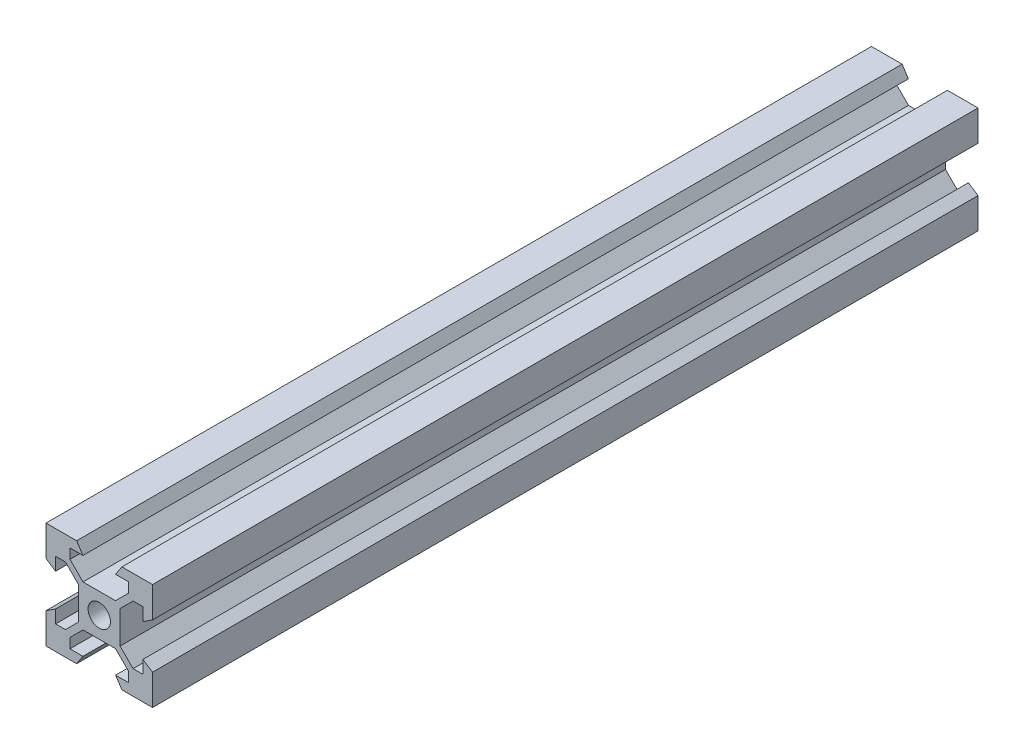
SolidWorks part; units mm, degrees
ref_plane "Front Plane" through (0, 0, 0) normal (0, 0, 1) x (1, 0, 0)
ref_plane "Top Plane" through (0, 0, 0) normal (0, 1, 0) x (1, 0, 0)
ref_plane "Right Plane" through (0, 0, 0) normal (1, 0, 0) x (0, 0, -1)
sketch "Sketch1" plane through (0, 0, 0) normal (0, 0, 1) x (1, 0, 0)
  line L0 (-10, 10) -> (-4.25, 10)
  line L1 (-4.25, 10) -> (-3.065, 8.2)
  line L2 (-3.065, 8.2) -> (-5.5, 8.2)
  line L3 (-5.5, 8.2) -> (-5.5, 6.3485)
  line L4 (-5.5, 6.3485) -> (-3.0515, 3.9)
  line L5 (-3.0515, 3.9) -> (0, 3.9)
  line L6 (-10, 10) -> (0, 0) construction
  line L7 (-3.9, 3.0515) -> (-3.9, 0)
  line L8 (-6.3485, 5.5) -> (-3.9, 3.0515)
  line L9 (-8.2, 3.065) -> (-8.2, 5.5)
  line L10 (-8.2, 5.5) -> (-6.3485, 5.5)
  line L11 (-10, 4.25) -> (-8.2, 3.065)
  line L12 (-10, 10) -> (-10, 4.25)
  line L13 (10, 10) -> (10, 4.25)
  line L14 (10, 10) -> (4.25, 10)
  line L15 (4.25, 10) -> (3.065, 8.2)
  line L16 (3.065, 8.2) -> (5.5, 8.2)
  line L17 (5.5, 8.2) -> (5.5, 6.3485)
  line L18 (8.2, 5.5) -> (6.3485, 5.5)
  line L19 (8.2, 3.065) -> (8.2, 5.5)
  line L20 (10, 4.25) -> (8.2, 3.065)
  line L21 (3.9, 3.0515) -> (3.9, 0)
  line L22 (6.3485, 5.5) -> (3.9, 3.0515)
  line L23 (5.5, 6.3485) -> (3.0515, 3.9)
  line L24 (3.0515, 3.9) -> (0, 3.9)
  line L25 (10, -10) -> (4.25, -10)
  line L26 (10, -10) -> (10, -4.25)
  line L27 (10, -4.25) -> (8.2, -3.065)
  line L28 (8.2, -3.065) -> (8.2, -5.5)
  line L29 (8.2, -5.5) -> (6.3485, -5.5)
  line L30 (5.5, -8.2) -> (5.5, -6.3485)
  line L31 (3.065, -8.2) -> (5.5, -8.2)
  line L32 (4.25, -10) -> (3.065, -8.2)
  line L33 (3.0515, -3.9) -> (0, -3.9)
  line L34 (5.5, -6.3485) -> (3.0515, -3.9)
  line L35 (6.3485, -5.5) -> (3.9, -3.0515)
  line L36 (3.9, -3.0515) -> (3.9, 0)
  line L37 (-10, -10) -> (-10, -4.25)
  line L38 (-10, -10) -> (-4.25, -10)
  line L39 (-4.25, -10) -> (-3.065, -8.2)
  line L40 (-3.065, -8.2) -> (-5.5, -8.2)
  line L41 (-5.5, -8.2) -> (-5.5, -6.3485)
  line L42 (-8.2, -5.5) -> (-6.3485, -5.5)
  line L43 (-8.2, -3.065) -> (-8.2, -5.5)
  line L44 (-10, -4.25) -> (-8.2, -3.065)
  line L45 (-3.9, -3.0515) -> (-3.9, 0)
  line L46 (-6.3485, -5.5) -> (-3.9, -3.0515)
  line L47 (-5.5, -6.3485) -> (-3.0515, -3.9)
  line L48 (-3.0515, -3.9) -> (0, -3.9)
  circle A0 centre (0, 0) radius 2.1
  point P58 (0, 0)
  dimension "D1" = 4.2
  dimension "D2" = 10
  dimension "D3" = 10
  dimension "D4" = 6.1
  dimension "D5" = 4.3
  dimension "D6" = 3.065
  dimension "D7" = 5.5
  dimension "D8" = 1.2
  dimension "D9" = 4.25
  dimension "D10" = 4
extrude "Boss-Extrude1" add sketch "Sketch1" along normal blind 155
